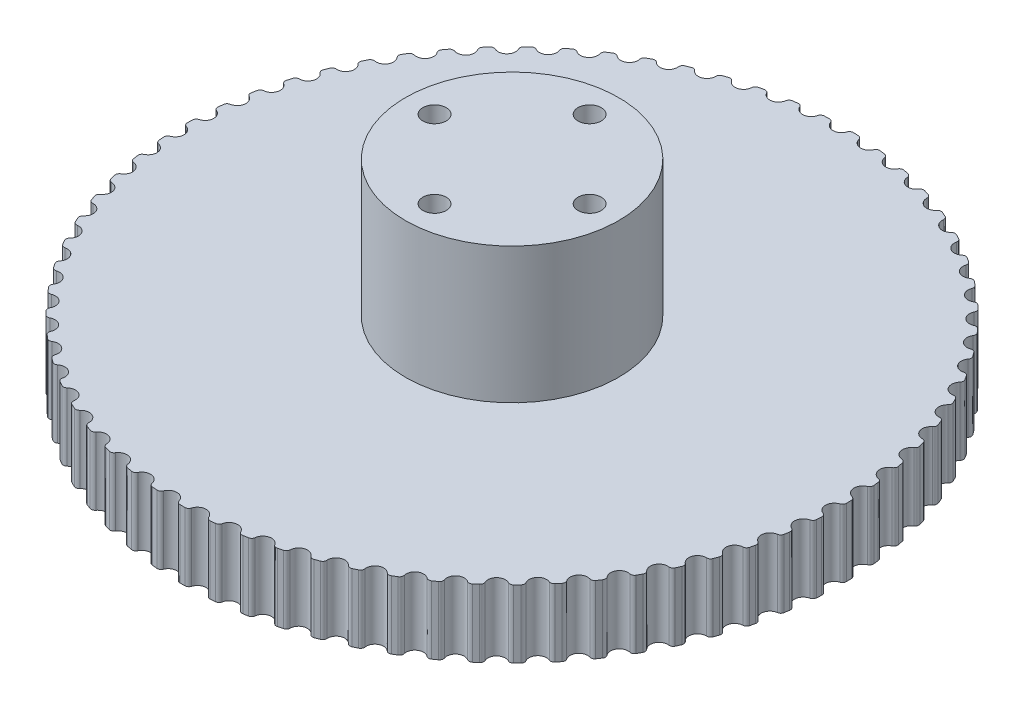
SolidWorks part; units mm, degrees
ref_plane "Front Plane" through (0, 0, 0) normal (0, 0, 1) x (1, 0, 0)
ref_plane "Top Plane" through (0, 0, 0) normal (0, 1, 0) x (1, 0, 0)
ref_plane "Right Plane" through (0, 0, 0) normal (1, 0, 0) x (0, 0, -1)
sketch "Sketch1" plane through (0, 0, 0) normal (0, 1, 0) x (1, 0, 0)
  circle A0 centre (0, 0) radius 34
  dimension "D1" = 68
extrude "Boss-Extrude1" add sketch "Sketch1" along normal blind 7
sketch "Sketch2" plane through (0, 7, 0) normal (0, 1, 0) x (1, 0, 0)
  circle A0 centre (0, 0) radius 11
  dimension "D1" = 22
extrude "Boss-Extrude2" add sketch "Sketch2" along normal blind 14
sketch "Sketch4" plane through (0, 0, 0) normal (0, -1, 0) x (1, 0, 0)
  line L0 (-8, 0) -> (0, 0) construction
  circle A0 centre (-8, 0) radius 2.25
  dimension "D1" = 4.5
  dimension "D2" = 8
extrude "Cut-Extrude1" cut sketch "Sketch4" against normal offset from surface (18 mm away) 3 up to face at (0, 21, 11)
hole_wizard "CSK for M2 Countersunk Flat Head Screw1" positions "3DSketch1" profile "Sketch5" countersink size "M2" standard "ISO" end condition through all
sketch3d "3DSketch1"
  line L0 (-8, 18, 0) -> (-8, 0, 0) construction
  point P0 (-8, 18, 0)
sketch "Sketch5" plane through (-8, 18, 0) normal (1, 0, 0) x (0, 0, -1)
  line L0 (0, 0) -> (0, 3)
  line L1 (0, 3) -> (1.2, 3)
  line L2 (1.2, 3) -> (1.2, 1)
  line L3 (1.2, 1) -> (2.2, 0)
  line L5 (2.2, 0) -> (0, 0)
  line L6 (-1.2, 1) -> (-2.2, 0) construction
  line L11 (0, -6.35) -> (0, 107.95) construction
  dimension "Thru Hole Dia." = 2.4
  dimension "Thru Hole Depth" = 3
  dimension "Near C'Sink Dia." = 4.4
  dimension "Near C'Sink Angle" = 90
pattern_circular "CirPattern1" count 4 over 360 about axis through (0, 7, 0) along (0, -1, 0) of "CSK for M2 Countersunk Flat Head Screw1", "Cut-Extrude1"
sketch "Sketch6" plane through (0, 7, 0) normal (0, 1, 0) x (1, 0, 0)
  arc A0 (0.8512, 33.7075) -> (-0.8512, 33.7075) centre (0, 34) cw
  circle A1 centre (0, 0) radius 34 construction
  arc A5 (1.2441, 33.9772) -> (0.8512, 33.7075) centre (1.2295, 33.5775) ccw
  arc A6 (-1.2441, 33.9772) -> (-0.8512, 33.7075) centre (-1.2295, 33.5775) cw
  arc A7 (1.2441, 33.9772) -> (-1.2441, 33.9772) centre (0, 0) ccw
  point P11 (0, 0)
  point P12 (0, 0)
  point P13 (-0.8445, 33.6886)
  point P14 (0, 0)
  point P15 (0, 0)
  dimension "D2" = 0.4
  dimension "D3" = 0.4
extrude "Cut-Extrude2" cut sketch "Sketch6" against normal through all
pattern_circular "CirPattern2" count 71 over 360 about axis through (0, 21, 0) along (0, -1, 0) of "Cut-Extrude2" reverse direction yes
